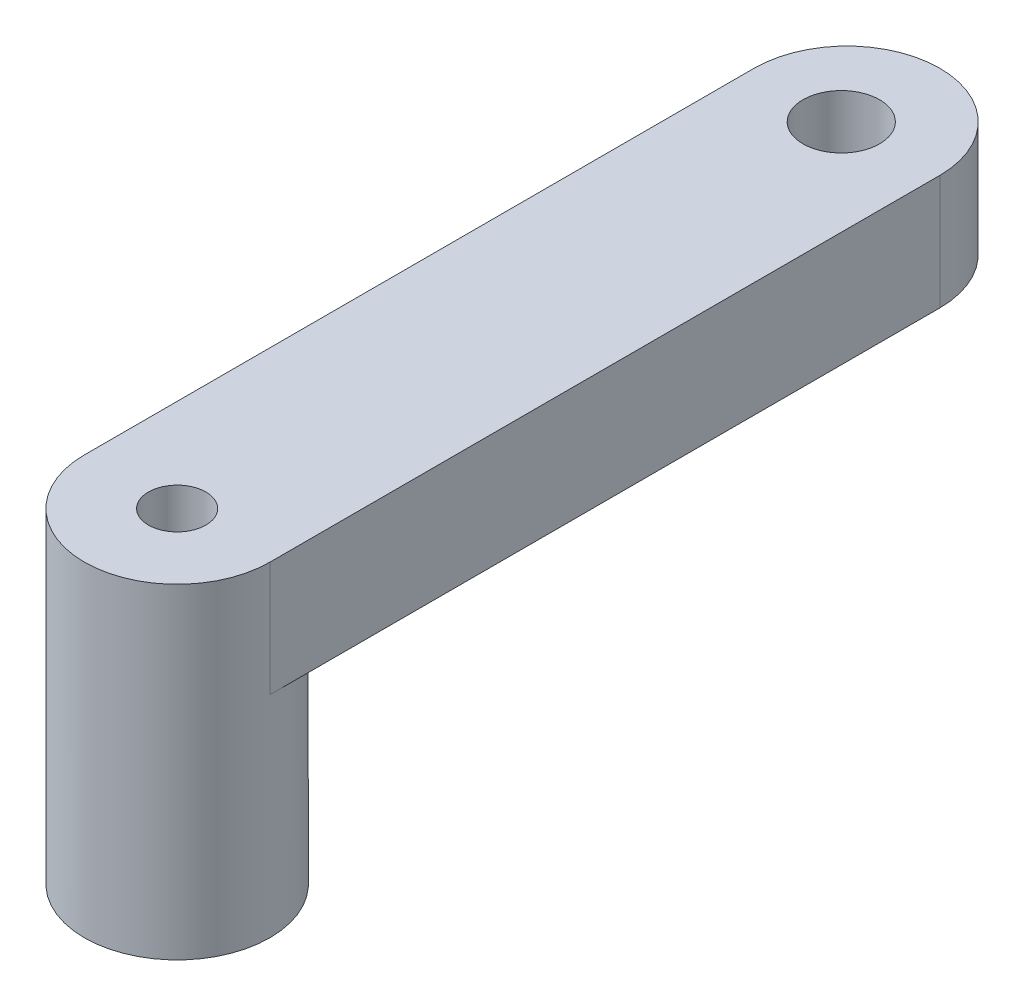
SolidWorks part; units mm, degrees
material "ABS"
ref_plane "Front Plane" through (0, 0, 0) normal (0, 0, 1) x (1, 0, 0)
ref_plane "Top Plane" through (0, 0, 0) normal (0, 1, 0) x (1, 0, 0)
ref_plane "Right Plane" through (0, 0, 0) normal (1, 0, 0) x (0, 0, -1)
sketch "Sketch1" plane through (0, 0, 0) normal (0, 1, 0) x (1, 0, 0)
  circle A0 centre (0, 0) radius 4.85
  circle A1 centre (0, 0) radius 1.5
  dimension "D1" = 9.7
  dimension "D2" = 3
extrude "Boss-Extrude1" add sketch "Sketch1" along normal blind 11
sketch "Sketch2" plane through (0, 11, 0) normal (0, 1, 0) x (1, 0, 0)
  line L0 (-4.85, 0) -> (-4.85, 35)
  line L2 (4.85, 35) -> (4.85, 0)
  circle A0 centre (0, 0) radius 4.85 construction
  arc A1 (-4.85, 0) -> (4.85, 0) centre (0, 0) ccw
  arc A3 (-4.85, 35) -> (4.85, 35) centre (0, 35) cw
  point P9 (-5, 35)
  dimension "D1" = 35
extrude "Boss-Extrude2" add sketch "Sketch2" along normal blind 6
sketch "Sketch3" plane through (0, 17, 0) normal (0, 1, 0) x (1, 0, 0)
  line L1 (4.85, 0) -> (4.85, 35) construction
  circle A0 centre (-0.15, 34.8523) radius 2
  arc A1 (4.85, 35) -> (-4.85, 35) centre (0, 35) ccw construction
  point P7 (0, 39.85)
  dimension "D1" = 4
  dimension "D2" = 5
  dimension "D3" = 5
extrude "Cut-Extrude1" cut sketch "Sketch3" against normal blind 7 contours A0
sketch "Sketch6" plane through (0, 11, 0) normal (0, -1, 0) x (1, 0, 0)
  circle A0 centre (0, 0) radius 1.5
extrude "Cut-Extrude2" cut sketch "Sketch6" against normal blind 10
